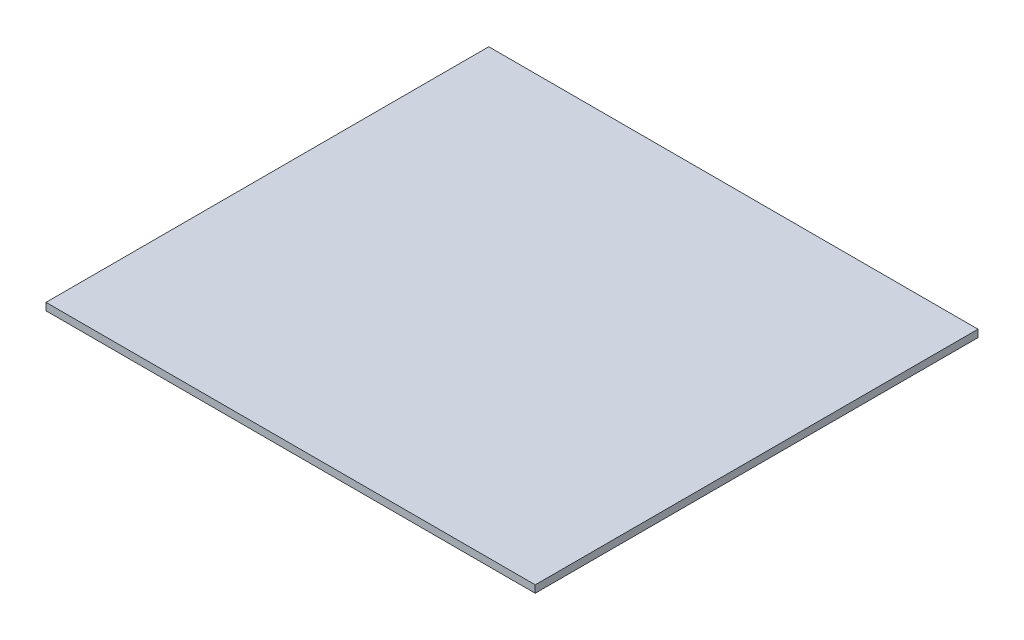
SolidWorks part; units mm, degrees
ref_plane "Front Plane" through (0, 0, 0) normal (0, 0, 1) x (1, 0, 0)
ref_plane "Top Plane" through (0, 0, 0) normal (0, 1, 0) x (1, 0, 0)
ref_plane "Right Plane" through (0, 0, 0) normal (1, 0, 0) x (0, 0, -1)
sketch "Sketch1" plane through (0, 0, 0) normal (0, 1, 0) x (1, 0, 0)
  line L1 (0, 0) -> (200, 0)
  line L2 (0, 0) -> (0, 181)
  line L3 (0, 181) -> (200, 181)
  line L4 (200, 0) -> (200, 181)
  dimension "D1" = 181
  dimension "D2" = 200
extrude "Boss-Extrude1" add sketch "Sketch1" along normal blind 3
